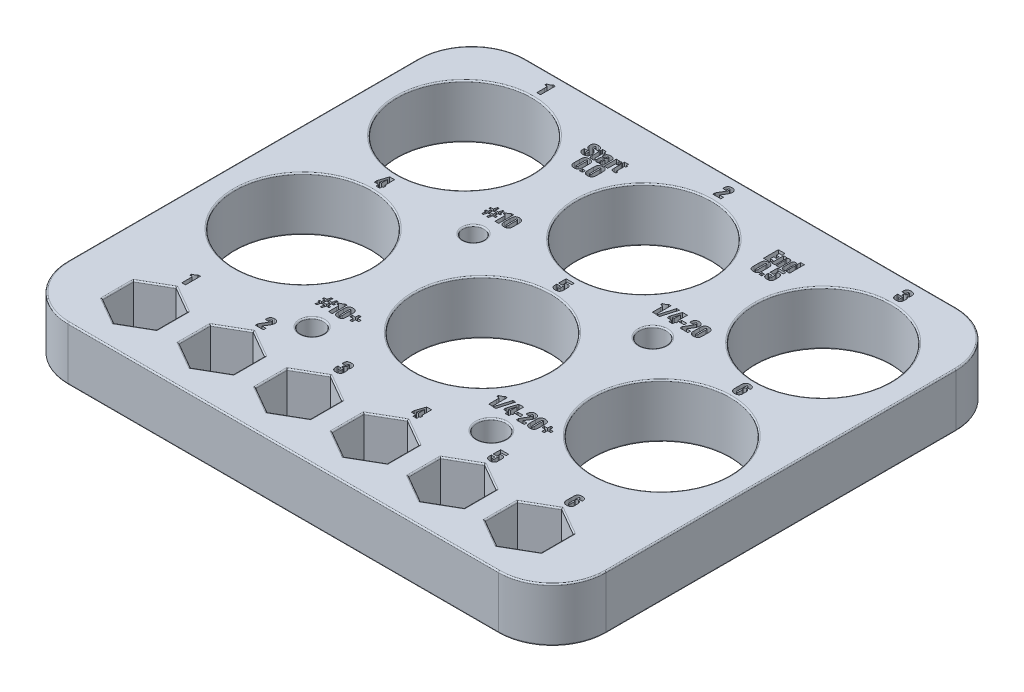
SolidWorks part; units mm, degrees
ref_plane "Front Plane" through (0, 0, 0) normal (0, 0, 1) x (1, 0, 0)
ref_plane "Top Plane" through (0, 0, 0) normal (0, 1, 0) x (1, 0, 0)
ref_plane "Right Plane" through (0, 0, 0) normal (1, 0, 0) x (0, 0, -1)
sketch "Sketch1" plane through (0, 0, 0) normal (0, 1, 0) x (1, 0, 0)
  line L0 (-63.5, -41.275) -> (-45.3571, -41.275) construction
  line L1 (-63.5, -53.975) -> (63.5, -53.975)
  line L2 (-63.5, -53.975) -> (-63.5, 53.975)
  line L3 (-63.5, 53.975) -> (63.5, 53.975)
  line L4 (63.5, -53.975) -> (63.5, 53.975)
  line L5 (-63.5, -53.975) -> (63.5, 53.975) construction
  line L6 (-63.5, 53.975) -> (63.5, -53.975) construction
  line L7 (-39.0071, -37.6088) -> (-45.3571, -33.9427)
  line L8 (-45.3571, -33.9427) -> (-51.7071, -37.6088)
  line L9 (-51.7071, -37.6088) -> (-51.7071, -44.9412)
  line L10 (-51.7071, -44.9412) -> (-45.3571, -48.6073)
  line L11 (-45.3571, -48.6073) -> (-39.0071, -44.9412)
  line L12 (-39.0071, -44.9412) -> (-39.0071, -37.6088)
  line L13 (-45.3571, -41.275) -> (-27.2143, -41.275) construction
  line L14 (-27.2143, -41.275) -> (-9.0714, -41.275) construction
  line L15 (-9.0714, -41.275) -> (9.0714, -41.275) construction
  line L16 (9.0714, -41.275) -> (27.2143, -41.275) construction
  line L17 (27.2143, -41.275) -> (45.3571, -41.275) construction
  line L18 (63.5, 31.115) -> (42.3333, 31.115) construction
  line L19 (42.3333, 31.115) -> (21.1667, 31.115) construction
  line L20 (21.1667, 31.115) -> (0, 31.115) construction
  line L21 (0, 31.115) -> (-21.1667, 31.115) construction
  line L22 (-21.1667, 31.115) -> (-42.3333, 31.115) construction
  line L23 (-42.3333, 31.115) -> (-63.5, 31.115) construction
  line L24 (-63.5, -6.985) -> (-42.3333, -6.985) construction
  line L25 (-20.8143, -44.97) -> (-20.8143, -37.58)
  line L26 (-20.8143, -37.58) -> (-27.2143, -33.8849)
  line L27 (-27.2143, -33.8849) -> (-33.6143, -37.58)
  line L28 (-33.6143, -37.58) -> (-33.6143, -44.97)
  line L29 (-33.6143, -44.97) -> (-27.2143, -48.6651)
  line L30 (-27.2143, -48.6651) -> (-20.8143, -44.97)
  line L31 (-2.6214, -44.9989) -> (-2.6214, -37.5511)
  line L32 (-2.6214, -37.5511) -> (-9.0714, -33.8272)
  line L33 (-9.0714, -33.8272) -> (-15.5214, -37.5511)
  line L34 (-15.5214, -37.5511) -> (-15.5214, -44.9989)
  line L35 (-15.5214, -44.9989) -> (-9.0714, -48.7228)
  line L36 (-9.0714, -48.7228) -> (-2.6214, -44.9989)
  line L37 (15.5714, -45.0278) -> (15.5714, -37.5222)
  line L38 (15.5714, -37.5222) -> (9.0714, -33.7694)
  line L39 (9.0714, -33.7694) -> (2.5714, -37.5222)
  line L40 (2.5714, -37.5222) -> (2.5714, -45.0278)
  line L41 (2.5714, -45.0278) -> (9.0714, -48.7806)
  line L42 (9.0714, -48.7806) -> (15.5714, -45.0278)
  line L43 (20.6643, -37.4934) -> (20.6643, -45.0566)
  line L44 (20.6643, -45.0566) -> (27.2143, -48.8383)
  line L45 (27.2143, -48.8383) -> (33.7643, -45.0566)
  line L46 (33.7643, -45.0566) -> (33.7643, -37.4934)
  line L47 (33.7643, -37.4934) -> (27.2143, -33.7117)
  line L48 (27.2143, -33.7117) -> (20.6643, -37.4934)
  line L49 (-42.3333, -6.985) -> (-21.1667, -6.985) construction
  line L50 (-21.1667, -6.985) -> (0, -6.985) construction
  line L51 (0, -6.985) -> (21.1667, -6.985) construction
  line L52 (21.1667, -6.985) -> (42.3333, -6.985) construction
  line L53 (42.3333, -6.985) -> (63.5, -6.985) construction
  line L54 (-42.3333, 31.115) -> (0, -6.985) construction
  line L55 (-42.3333, -6.985) -> (0, 31.115) construction
  line L56 (0, 31.115) -> (42.3333, -6.985) construction
  line L57 (0, -6.985) -> (42.3333, 31.115) construction
  line L58 (45.3571, -41.275) -> (63.5, -41.275) construction
  line L71 (-21.1667, -6.985) -> (-21.1667, -26.035) construction
  line L72 (38.7571, -37.4645) -> (38.7571, -45.0855)
  line L73 (38.7571, -45.0855) -> (45.3571, -48.896)
  line L74 (45.3571, -48.896) -> (51.9571, -45.0855)
  line L75 (51.9571, -45.0855) -> (51.9571, -37.4645)
  line L76 (51.9571, -37.4645) -> (45.3571, -33.654)
  line L77 (45.3571, -33.654) -> (38.7571, -37.4645)
  line L78 (-21.1667, -26.035) -> (21.1667, -26.035) construction
  line L79 (21.1667, -26.035) -> (21.1667, -6.985) construction
  line L80 (-21.1667, 12.065) -> (-21.1667, -6.985) construction
  line L81 (21.1667, 12.065) -> (21.1667, -6.985) construction
  circle A0 centre (-42.3333, 31.115) radius 15.875
  circle A1 centre (-45.3571, -41.275) radius 6.35 construction
  circle A2 centre (0, 31.115) radius 15.925
  circle A3 centre (42.3333, 31.115) radius 15.975
  circle A4 centre (-27.2143, -41.275) radius 6.4 construction
  circle A5 centre (-9.0714, -41.275) radius 6.45 construction
  circle A6 centre (9.0714, -41.275) radius 6.5 construction
  circle A7 centre (27.2143, -41.275) radius 6.55 construction
  circle A10 centre (-42.3333, -6.985) radius 16.075
  circle A11 centre (0, -6.985) radius 16.075
  circle A12 centre (42.3333, -6.985) radius 16.125
  circle A13 centre (-21.1667, 12.065) radius 1.27
  circle A14 centre (21.1667, 12.065) radius 1.27
  circle A16 centre (45.3571, -41.275) radius 6.6 construction
  circle A17 centre (-21.1667, -26.035) radius 1.27
  circle A18 centre (21.1667, -26.035) radius 1.27
  point P0 (0, 0)
  dimension "D4" = 31.75
  dimension "D13" = 31.85
  dimension "D14" = 31.95
  dimension "D12" = 32.15
  dimension "D15" = 32.15
  dimension "D16" = 32.25
  dimension "D17" = 2.54
  dimension "D1" = 127
  dimension "D2" = 107.95
  dimension "D5" = 22.86
  dimension "D7" = 12.8
  dimension "D8" = 12.9
  dimension "D9" = 13
  dimension "D10" = 13.1
  dimension "D3" = 12.7
  dimension "D11" = 60.96
  dimension "D6" = 13.2
  dimension "D18" = 12.7
extrude "Test Plate" add sketch "Sketch1" along normal blind 12.7
hole_wizard "1/4 (0.25) Thru Hole" positions "Sketch6" profile "Sketch5" hole size "1/4" standard "ANSI Inch" end condition through all
sketch "Sketch6" plane through (0, 12.7, 0) normal (0, 1, 0) x (1, 0, 0)
  point P0 (21.1667, 12.065)
  point P3 (21.1667, -26.035)
sketch "Sketch5" plane through (21.1667, 12.7, -12.065) normal (1, 0, 0) x (0, 0, 1)
  line L0 (0, 0) -> (0, 12.7)
  line L1 (0, 12.7) -> (3.175, 12.7)
  line L2 (3.175, 12.7) -> (3.175, 0)
  line L5 (3.175, 0) -> (0, 0)
  line L11 (0, -6.35) -> (0, 107.95) construction
  dimension "Thru Hole Dia." = 6.35
  dimension "Thru Hole Depth" = 12.7
hole_wizard "#10 (0.1935) Thru Hole" positions "Sketch7" profile "Sketch8" hole size "#10" standard "ANSI Inch" end condition through all
sketch "Sketch7" plane through (0, 12.7, 0) normal (0, 1, 0) x (1, 0, 0)
  point P0 (-21.1667, 12.065)
  point P3 (-21.1667, -26.035)
sketch "Sketch8" plane through (-21.1667, 12.7, -12.065) normal (1, 0, 0) x (0, 0, 1)
  line L0 (0, 0) -> (0, 12.7)
  line L1 (0, 12.7) -> (2.4574, 12.7)
  line L2 (2.4574, 12.7) -> (2.4574, 0)
  line L5 (2.4574, 0) -> (0, 0)
  line L11 (0, -6.35) -> (0, 107.95) construction
  dimension "Thru Hole Dia." = 4.9149
  dimension "Thru Hole Depth" = 12.7
sketch "Sketch9" plane through (0, 12.7, 0) normal (0, 1, 0) x (1, 0, 0)
  circle A0 centre (-21.1667, -26.035) radius 2.7075
  circle A1 centre (21.1667, -26.035) radius 3.425
  circle A2 centre (-21.1667, -26.035) radius 2.4574 construction
  circle A3 centre (21.1667, -26.035) radius 3.175 construction
  dimension "D1" = 0.25
  dimension "D2" = 0.25
extrude "Half Max Tolerance Bolt Holes" cut sketch "Sketch9" against normal through all
fillet "Corner Fillet" radius 12.7 4 edges at (-63.5, 6.35, -53.975) (63.5, 6.35, -53.975) (63.5, 6.35, 53.975) (-63.5, 6.35, 53.975)
fillet "Face Smooth" radius 0.3175 108 edges at (42.3333, 12.7, 23.11) (0, 12.7, 23.06) (-42.3333, 12.7, 23.06) (20.6643, 12.7, 41.275) (23.9393, 12.7, 46.9475) (30.4893, 12.7, 46.9475) (33.7643, 12.7, 41.275) (30.4893, 12.7, 35.6025) (23.9393, 12.7, 35.6025) (-2.6214, 12.7, 41.275) (-5.8464, 12.7, 35.6891) (-12.2964, 12.7, 35.6891) (-15.5214, 12.7, 41.275) (-12.2964, 12.7, 46.8609) (-5.8464, 12.7, 46.8609) (-42.1821, 12.7, 35.7757) (-48.5321, 12.7, 35.7757) (-51.7071, 12.7, 41.275) (-48.5321, 12.7, 46.7743) (-42.1821, 12.7, 46.7743) (-39.0071, 12.7, 41.275) (59.7803, 12.7, -50.2553) (63.5, 12.7, 0) (59.7803, 12.7, 50.2553) (0, 12.7, 53.975) (-59.7803, 12.7, 50.2553) (-63.5, 12.7, 0) (-59.7803, 12.7, -50.2553) (0, 12.7, -53.975) (0, 12.7, -15.19) (-42.3333, 12.7, -15.24) (42.3333, 12.7, -15.14) (-20.8143, 12.7, 41.275) (-24.0143, 12.7, 35.7324) (-30.4143, 12.7, 35.7324) (-33.6143, 12.7, 41.275) (-30.4143, 12.7, 46.8176) (-24.0143, 12.7, 46.8176) (15.5714, 12.7, 41.275) (12.3214, 12.7, 35.6458) (5.8214, 12.7, 35.6458) (2.5714, 12.7, 41.275) (5.8214, 12.7, 46.9042) (12.3214, 12.7, 46.9042) (42.3333, 0, 23.11) (-42.3333, 0, 23.06) (-42.3333, 0, -15.24) (-59.7803, 0, 50.2553) (0, 0, 53.975) (59.7803, 0, 50.2553) (63.5, 0, 0) (59.7803, 0, -50.2553) (0, 0, -53.975) (-59.7803, 0, -50.2553) (-63.5, 0, 0) (0, 0, -15.19) (42.3333, 0, -15.14) (-48.5321, 0, 46.7743) (-51.7071, 0, 41.275) (-48.5321, 0, 35.7757) (-42.1821, 0, 35.7757) (-39.0071, 0, 41.275) (-42.1821, 0, 46.7743) (-33.6143, 0, 41.275) (-30.4143, 0, 35.7324) (-24.0143, 0, 35.7324) (-20.8143, 0, 41.275) (-24.0143, 0, 46.8176) (-30.4143, 0, 46.8176) (-15.5214, 0, 41.275) (-12.2964, 0, 35.6891) (-5.8464, 0, 35.6891) (-2.6214, 0, 41.275) (-5.8464, 0, 46.8609) (-12.2964, 0, 46.8609) (2.5714, 0, 41.275) (5.8214, 0, 35.6458) (12.3214, 0, 35.6458) (15.5714, 0, 41.275) (12.3214, 0, 46.9042) (5.8214, 0, 46.9042) (33.7643, 0, 41.275) (30.4893, 0, 46.9475) (23.9393, 0, 46.9475) (20.6643, 0, 41.275) (23.9393, 0, 35.6025) (30.4893, 0, 35.6025) (0, 0, 23.06) (-21.1667, 12.7, -9.6075) (21.1667, 12.7, -8.89) (-21.1667, 0, -9.6076) (21.1667, 0, -8.89) (38.7571, 12.7, 41.275) (42.0571, 12.7, 46.9908) (48.6571, 12.7, 46.9908) (51.9571, 12.7, 41.275) (48.6571, 12.7, 35.5592) (42.0571, 12.7, 35.5592) (51.9571, 0, 41.275) (48.6571, 0, 46.9908) (42.0571, 0, 46.9908) (38.7571, 0, 41.275) (42.0571, 0, 35.5592) (48.6571, 0, 35.5592) (21.1667, 12.7, 29.46) (-21.1667, 12.7, 28.7425) (21.1667, 0, 29.46) (-21.1667, 0, 28.7425)
sketch "Sketch10" plane through (0, 12.7, 0) normal (0, 1, 0) x (1, 0, 0)
  line L0 (-42.3333, 31.115) -> (-42.3333, 48.387) construction
  line L1 (0, 31.115) -> (0, 48.387) construction
  line L2 (42.3333, 31.115) -> (42.3333, 48.387) construction
  line L3 (-45.5083, 48.387) -> (-39.1583, 48.387) construction
  line L4 (-3.175, 48.387) -> (3.175, 48.387) construction
  line L5 (39.1583, 48.387) -> (45.5083, 48.387) construction
  line L7 (-42.3333, -6.985) -> (-42.3333, 10.287) construction
  line L8 (0, -6.985) -> (0, 10.287) construction
  line L9 (42.3333, -6.985) -> (42.3333, 10.287) construction
  line L10 (-45.5083, 10.287) -> (-39.1583, 10.287) construction
  line L11 (-3.175, 10.287) -> (3.175, 10.287) construction
  line L12 (45.5083, 10.287) -> (39.1583, 10.287) construction
  line L13 (-51.7071, -41.275) -> (-39.0071, -41.275) construction
  line L14 (-51.7071, -37.6088) -> (-51.7071, -44.9412) construction
  line L15 (-39.0071, -44.9412) -> (-39.0071, -37.6088) construction
  line L16 (-33.6143, -41.275) -> (-20.8143, -41.275) construction
  line L17 (-33.6143, -37.58) -> (-33.6143, -44.97) construction
  line L18 (-20.8143, -44.97) -> (-20.8143, -37.58) construction
  line L19 (-15.5214, -41.275) -> (-2.6214, -41.275) construction
  line L20 (-15.5214, -37.5511) -> (-15.5214, -44.9989) construction
  line L21 (-2.6214, -44.9989) -> (-2.6214, -37.5511) construction
  line L22 (2.5714, -41.275) -> (15.5714, -41.275) construction
  line L23 (2.5714, -37.5222) -> (2.5714, -45.0278) construction
  line L24 (15.5714, -45.0278) -> (15.5714, -37.5222) construction
  line L25 (20.6643, -41.275) -> (33.7643, -41.275) construction
  line L26 (20.6643, -37.4934) -> (20.6643, -45.0566) construction
  line L27 (33.7643, -45.0566) -> (33.7643, -37.4934) construction
  line L28 (38.7571, -41.275) -> (51.9571, -41.275) construction
  line L29 (38.7571, -37.4645) -> (38.7571, -45.0855) construction
  line L30 (51.9571, -45.0855) -> (51.9571, -37.4645) construction
  line L31 (21.1667, -26.035) -> (21.1667, -20.955) construction
  line L32 (-21.1667, -26.035) -> (-21.1667, -20.955) construction
  line L33 (-21.1667, 12.065) -> (-21.1667, 17.145) construction
  line L34 (21.1667, 12.065) -> (21.1667, 17.145) construction
  line L35 (-27.5167, -20.955) -> (-14.8167, -20.955) construction
  line L36 (-27.5167, 17.145) -> (-14.8167, 17.145) construction
  line L37 (14.8167, 17.145) -> (27.5167, 17.145) construction
  line L38 (14.8167, -20.955) -> (27.5167, -20.955) construction
  line L39 (-45.3571, -41.275) -> (-45.3571, -32.385) construction
  line L40 (-27.2143, -41.275) -> (-27.2143, -32.385) construction
  line L41 (-9.0714, -41.275) -> (-9.0714, -32.385) construction
  line L42 (9.0714, -41.275) -> (9.0714, -32.385) construction
  line L43 (27.2143, -41.275) -> (27.2143, -32.385) construction
  line L44 (45.3571, -41.275) -> (45.3571, -32.385) construction
  line L45 (-48.5321, -32.385) -> (-42.1821, -32.385) construction
  line L46 (-30.3893, -32.385) -> (-24.0393, -32.385) construction
  line L47 (-12.2464, -32.385) -> (-5.8964, -32.385) construction
  line L48 (5.8964, -32.385) -> (12.2464, -32.385) construction
  line L49 (24.0393, -32.385) -> (30.3893, -32.385) construction
  line L50 (42.1821, -32.385) -> (48.5321, -32.385) construction
  line L51 (-21.1667, 17.145) -> (-21.1667, 53.975) construction
  line L52 (63.5, 53.975) -> (-63.5, 53.975) construction
  line L53 (21.1667, 17.145) -> (21.1667, 53.975) construction
  line L54 (-26.2467, 41.275) -> (-16.0867, 41.275) construction
  line L55 (16.0867, 41.275) -> (26.2467, 41.275) construction
  line L56 (-26.2467, 37.465) -> (-16.0867, 37.465) construction
  line L57 (26.2467, 37.465) -> (16.0867, 37.465) construction
  text T0 "1" font "Impact" height 3.5
  text T1 "2" font "Impact" height 3.5
  text T2 "Start" font "Impact" height 3.5
  text T3 "0.0" font "Impact" height 3.5
  text T4 "End" font "Impact" height 3.5
  text T5 "0.5" font "Impact" height 3.5
  text T6 "#10" font "Impact" height 3.5
  text T7 "1/4-20" font "Impact" height 3.5
  text T8 "#10+" font "Impact" height 3.5
  text T9 "1/4-20+" font "Impact" height 3.5
  text T10 "1" font "Impact" height 3.5
  text T11 "2" font "Impact" height 3.5
  text T12 "3" font "Impact" height 3.5
  text T13 "4" font "Impact" height 3.5
  text T14 "5" font "Impact" height 3.5
  text T15 "6" font "Impact" height 3.5
  text T16 "3" font "Impact" height 3.5
  text T17 "4" font "Impact" height 3.5
  text T18 "5" font "Impact" height 3.5
  text T19 "6" font "Impact" height 3.5
  point P13 (-42.3333, 48.387)
  point P16 (0, 48.387)
  point P19 (42.3333, 48.387)
  point P32 (-42.3333, 10.287)
  point P35 (0, 10.287)
  point P38 (42.3333, 10.287)
  point P91 (-21.1667, -20.955)
  point P94 (-21.1667, 17.145)
  point P97 (21.1667, 17.145)
  point P100 (21.1667, -20.955)
  point P115 (-45.3571, -32.385)
  point P118 (-27.2143, -32.385)
  point P121 (-9.0714, -32.385)
  point P124 (9.0714, -32.385)
  point P127 (27.2143, -32.385)
  point P130 (45.3571, -32.385)
  point P137 (-21.1667, 41.275)
  point P140 (21.1667, 41.275)
  point P144 (-21.1667, 37.465)
  point P147 (21.1667, 37.465)
  dimension "D1" = 6.35
  dimension "D2" = 17.272
  dimension "D3" = 6.35
  dimension "D4" = 8.89
  dimension "D5" = 5.08
  dimension "D6" = 12.7
  dimension "D7" = 10.16
  dimension "D8" = 12.7
  dimension "D9" = 3.81
extrude "Labeling" cut sketch "Sketch10" against normal blind 2.54
equation "\"Start Tolerance\"= 0.0mm'First Hole Offset."
equation "\"End Tolerance\"= 0.5mm'Final Hole Offset. In between is Interpolated"
equation "\"Hole Diameter\"= 1.25in"
equation "\"Hex Width\"= .5in"
equation "\"D4@Sketch1\"=\"Hole Diameter\" + \"Start Tolerance\""
equation "\"D13@Sketch1\"=\"Hole Diameter\" + 0.2 * (\"End Tolerance\" - \"Start Tolerance\")"
equation "\"D14@Sketch1\"=\"Hole Diameter\" + 0.4 * (\"End Tolerance\" - \"Start Tolerance\")"
equation "\"D12@Sketch1\"=\"Hole Diameter\" + 0.8 * (\"End Tolerance\" - \"Start Tolerance\")"
equation "\"D16@Sketch1\"=\"Hole Diameter\" + \"End Tolerance\""
equation "\"D15@Sketch1\"=\"Hole Diameter\" + 0.8 * (\"End Tolerance\" - \"Start Tolerance\")"
equation "\"D3@Sketch1\"=\"Hex Width\" + \"Start Tolerance\""
equation "\"D7@Sketch1\"=\"Hex Width\" + 0.2 * (\"End Tolerance\" - \"Start Tolerance\")"
equation "\"D8@Sketch1\"=\"Hex Width\" + 0.4 * (\"End Tolerance\" - \"Start Tolerance\")"
equation "\"D9@Sketch1\"=\"Hex Width\" + 0.6 * (\"End Tolerance\" - \"Start Tolerance\")"
equation "\"D10@Sketch1\"=\"Hex Width\" + 0.8 * (\"End Tolerance\" - \"Start Tolerance\")"
equation "\"D6@Sketch1\"=\"Hex Width\" + \"End Tolerance\""
equation "\"D1@Sketch9\"=0.5 * (\"End Tolerance\" - \"Start Tolerance\")"
equation "\"D2@Sketch9\"=0.5 * (\"End Tolerance\" - \"Start Tolerance\")"
